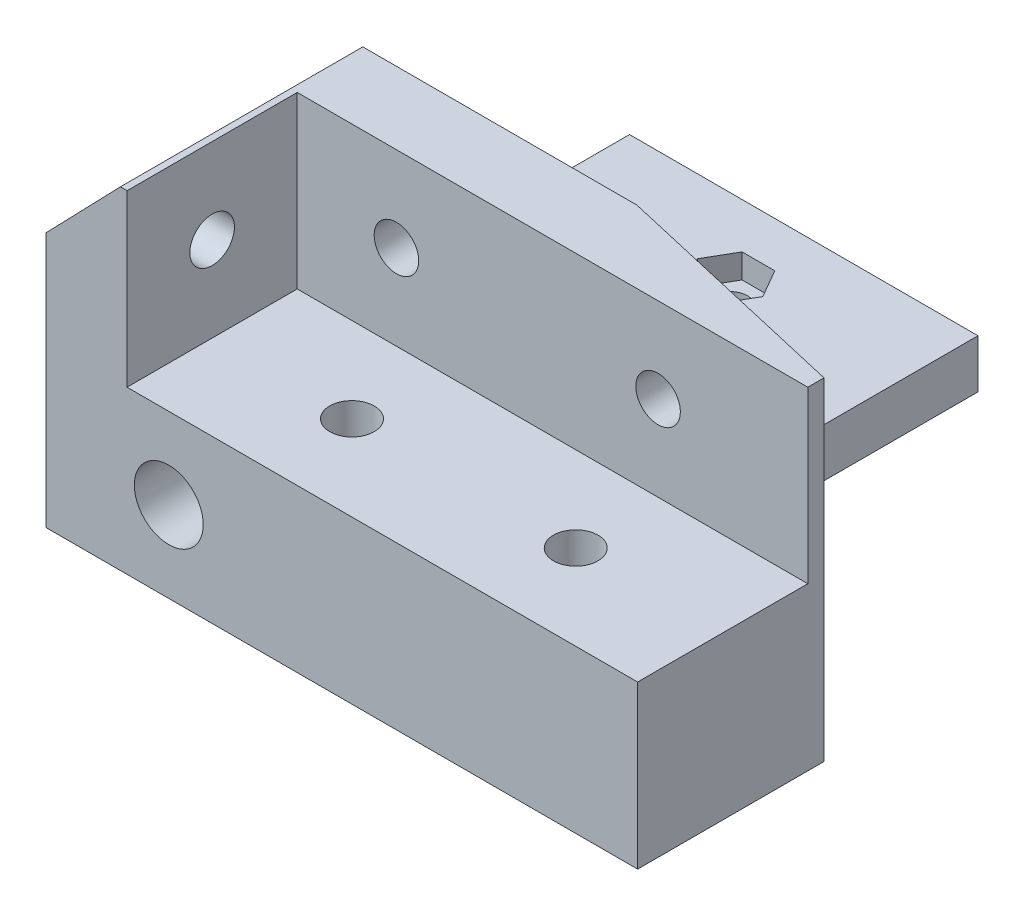
SolidWorks part; units mm, degrees
ref_plane "Спереди" through (0, 0, 0) normal (0, 0, 1) x (1, 0, 0)
ref_plane "Сверху" through (0, 0, 0) normal (0, 1, 0) x (1, 0, 0)
ref_plane "Справа" through (0, 0, 0) normal (1, 0, 0) x (0, 0, -1)
sketch "Эскиз1" plane through (0, 0, 0) normal (0, 1, 0) x (1, 0, 0)
  line L0 (-31.7371, -43.025) -> (41.2629, -43.025)
  line L1 (-31.7371, 28.975) -> (11.2629, 28.975)
  line L2 (-31.7371, 28.975) -> (-31.7371, -43.025)
  line L4 (11.2629, 28.975) -> (11.2629, -13.1094)
  line L5 (41.2629, -43.025) -> (41.2629, -20.025)
  line L6 (55.066, 26.975) -> (55.066, -15.1094) construction
  line L7 (41.2629, -20.025) -> (11.2629, -13.1094)
  circle A0 centre (-10.2371, 19.8798) radius 2.15
  circle A1 centre (0, 0) radius 2.15
  dimension "D1" = 4.3
  dimension "D2" = 4.3
extrude "Бобышка-Вытянуть1" add sketch "Эскиз1" along normal blind 6
sketch "Эскиз2" plane through (0, 6, 0) normal (0, 1, 0) x (1, 0, 0)
  line L0 (41.2629, -20.025) -> (11.2629, -13.1094)
  line L1 (11.2629, -13.1094) -> (-31.7371, -13.1094)
  line L2 (-31.7371, 28.975) -> (-31.7371, -43.025) construction
  line L3 (-31.7371, -13.1094) -> (-31.7371, -43.025)
  line L4 (-31.7371, -43.025) -> (41.2629, -43.025)
  line L5 (41.2629, -43.025) -> (41.2629, -20.025)
extrude "Бобышка-Вытянуть2" add sketch "Эскиз2" along normal blind 35
sketch "Эскиз3" plane through (0, 41, 0) normal (0, 1, 0) x (1, 0, 0)
  line L1 (41.2629, -43.025) -> (-21.7371, -43.025)
  line L2 (41.2629, -43.025) -> (41.2629, -22.025)
  line L3 (41.2629, -22.025) -> (-21.7371, -22.025)
  line L4 (-21.7371, -43.025) -> (-21.7371, -22.025)
  dimension "D1" = 21
  dimension "D2" = 63
extrude "Вырез-Вытянуть1" cut sketch "Эскиз3" against normal blind 21
sketch "Эскиз4" plane through (-21.7371, 0, 0) normal (1, 0, 0) x (0, 0, -1)
  circle A0 centre (-32.525, 30.5) radius 2.75
  dimension "D1" = 5.5
extrude "Вырез-Вытянуть2" cut sketch "Эскиз4" against normal through all
chamfer "Фаска1" distance 9.5 angle 44 1 edges at (-31.7371, 41, 28.0672) first distance on face at (-31.7371, 30.5, 29.775)
sketch "Эскиз5" plane through (-21.7371, 0, 0) normal (1, 0, 0) x (0, 0, -1)
  circle A0 centre (-32.525, 30.5) radius 4.25
  dimension "D1" = 8.5
extrude "Вырез-Вытянуть3" cut sketch "Эскиз5" along normal blind 5 from offset 10 offset against normal yes
sketch "Эскиз6" plane through (0, 0, 22.025) normal (0, 0, 1) x (1, 0, 0)
  circle A0 centre (-9.4957, 30.5) radius 2.75
  circle A1 centre (22.7857, 30.5) radius 2.75
  dimension "D1" = 5.5
  dimension "D2" = 5.5
extrude "Вырез-Вытянуть4" cut sketch "Эскиз6" against normal through all
sketch "Эскиз7" plane through (0, 0, 22.025) normal (0, 0, 1) x (1, 0, 0)
  circle A0 centre (-9.4957, 30.5) radius 4.25
  circle A1 centre (22.7857, 30.5) radius 4.25
  dimension "D1" = 8.5
  dimension "D2" = 8.5
extrude "Вырез-Вытянуть5" cut sketch "Эскиз7" against normal blind 5 from offset 4 offset against normal yes
sketch "Эскиз8" plane through (0, 20, 0) normal (0, 1, 0) x (1, 0, 0)
  circle A0 centre (-4.4832, -32.525) radius 2.75
  circle A1 centre (23.1264, -32.525) radius 2.75
  dimension "D1" = 5.5
  dimension "D2" = 5.5
extrude "Вырез-Вытянуть6" cut sketch "Эскиз8" against normal through all
sketch "Эскиз10" plane through (0, 0, 0) normal (0, -1, 0) x (1, 0, 0)
  circle A0 centre (23.1264, 32.525) radius 4.25
  circle A1 centre (-4.4832, 32.525) radius 4.25
  dimension "D1" = 8.5
  dimension "D2" = 8.5
extrude "Вырез-Вытянуть7" cut sketch "Эскиз10" against normal blind 15.5
sketch "Эскиз11" plane through (0, 0, 43.025) normal (0, 0, 1) x (1, 0, 0)
  line L0 (-21.7371, -4.2335) -> (-16.5871, -4.2335) construction
  circle A1 centre (-16.5871, 10) radius 4.25
  dimension "D3" = 8.5
  dimension "D2" = 5.15
extrude "Вырез-Вытянуть8" cut sketch "Эскиз11" against normal blind 20
ref_plane "Плоскость1" through (51.2629, 0, 0) normal (1, 0, 0) x (0, 0, -1)
sketch "Эскиз12" plane through (0, 6, 0) normal (0, 1, 0) x (1, 0, 0)
  line L1 (-6.1956, 19.8798) -> (-8.2164, 23.3798)
  line L2 (-8.2164, 23.3798) -> (-12.2578, 23.3798)
  line L3 (-12.2578, 23.3798) -> (-14.2786, 19.8798)
  line L4 (-14.2786, 19.8798) -> (-12.2578, 16.3798)
  line L5 (-12.2578, 16.3798) -> (-8.2164, 16.3798)
  line L6 (-8.2164, 16.3798) -> (-6.1956, 19.8798)
  line L7 (4.0415, 0) -> (2.0207, 3.5)
  line L8 (2.0207, 3.5) -> (-2.0207, 3.5)
  line L9 (-2.0207, 3.5) -> (-4.0415, 0)
  line L10 (-4.0415, 0) -> (-2.0207, -3.5)
  line L11 (-2.0207, -3.5) -> (2.0207, -3.5)
  line L12 (2.0207, -3.5) -> (4.0415, 0)
  circle A0 centre (-10.2371, 19.8798) radius 3.5 construction
  circle A1 centre (0, 0) radius 3.5 construction
extrude "Вырез-Вытянуть9" cut sketch "Эскиз12" against normal blind 3
